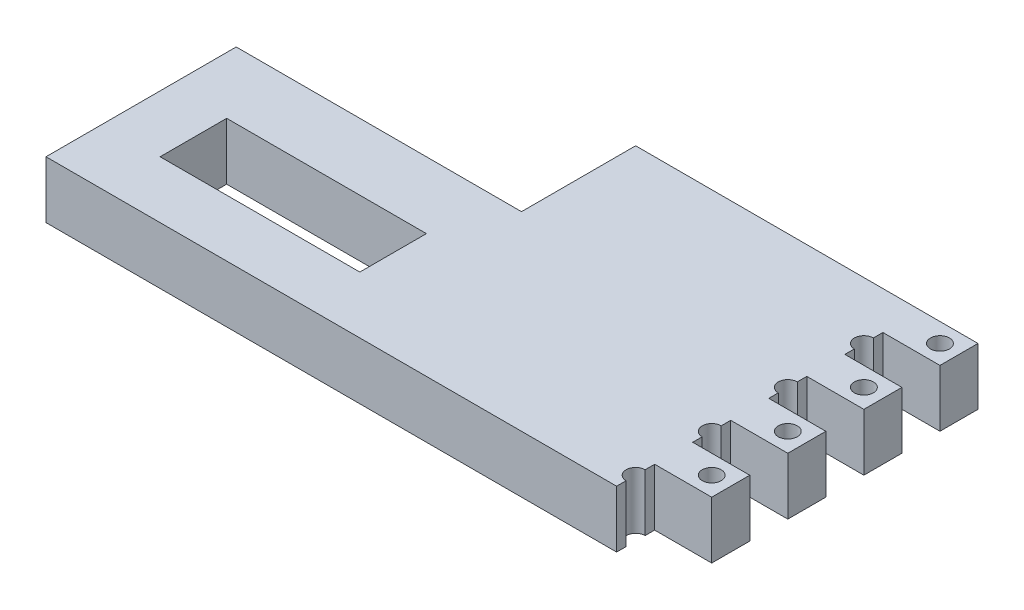
SolidWorks part; units mm, degrees
ref_plane "Front Plane" through (0, 0, 0) normal (0, 0, 1) x (1, 0, 0)
ref_plane "Top Plane" through (0, 0, 0) normal (0, 1, 0) x (1, 0, 0)
ref_plane "Right Plane" through (0, 0, 0) normal (1, 0, 0) x (0, 0, -1)
sketch "Sketch1" plane through (0, 0, 0) normal (0, 1, 0) x (1, 0, 0)
  line L0 (-30, 0) -> (0, 0)
  line L1 (0, 0) -> (0, 12)
  line L2 (0, 12) -> (36, 12)
  line L3 (36, 0) -> (36, 4)
  line L4 (36, 4) -> (30, 4)
  line L5 (30, 4) -> (30, 8)
  line L6 (30, 8) -> (36, 8)
  line L7 (36, 8) -> (36, 12)
  line L8 (30, -4) -> (36, -4)
  line L9 (36, -4) -> (36, -8)
  line L10 (36, -8) -> (30, -8)
  line L11 (30, -12) -> (30, -8)
  line L12 (36, 0) -> (30, 0)
  line L13 (30, 0) -> (30, -4)
  line L14 (30, -20) -> (-30, -20)
  line L15 (-30, -20) -> (-30, 0)
  line L16 (30, -12) -> (36, -12)
  line L17 (36, -12) -> (36, -16)
  line L18 (36, -16) -> (30, -16)
  line L19 (30, -16) -> (30, -20)
  dimension "D1" = 4
  dimension "D2" = 30
  dimension "D3" = 12
  dimension "D4" = 6
  dimension "D5" = 4
  dimension "D6" = 4
  dimension "D7" = 20
  dimension "D8" = 30
  dimension "D9" = 4
  dimension "D10" = 4
  dimension "D11" = 4
  dimension "D12" = 4
extrude "Boss-Extrude1" add sketch "Sketch1" along normal blind 6
sketch "Sketch2" plane through (0, 6, 0) normal (0, 1, 0) x (1, 0, 0)
  line L0 (0, 12) -> (0, 0) construction
  line L1 (-24, -7) -> (-3, -7)
  line L2 (-24, -7) -> (-24, -14)
  line L3 (-24, -14) -> (-3, -14)
  line L4 (-3, -7) -> (-3, -14)
  line L5 (-30, -20) -> (30, -20) construction
  dimension "D1" = 7
  dimension "D2" = 21
  dimension "D3" = 3
  dimension "D4" = 6
extrude "Cut-Extrude1" cut sketch "Sketch2" against normal through all
sketch "Sketch3" plane through (0, 6, 0) normal (0, 1, 0) x (1, 0, 0)
  line L0 (36, 8) -> (36, 12) construction
  line L1 (36, 0) -> (36, 4) construction
  line L2 (36, -8) -> (36, -4) construction
  line L3 (36, -16) -> (36, -12) construction
  line L4 (30, 4) -> (30, 8) construction
  line L5 (30, -4) -> (30, 0) construction
  line L6 (30, -12) -> (30, -8) construction
  line L7 (30, -20) -> (30, -16) construction
  circle A0 centre (34, 10) radius 1
  circle A1 centre (34, 2) radius 1
  circle A2 centre (34, -6) radius 1
  circle A3 centre (34, -14) radius 1
  circle A4 centre (30, 6) radius 1
  circle A5 centre (30, -2) radius 1
  circle A6 centre (30, -10) radius 1
  circle A7 centre (30, -18) radius 1
  point P4 (36, 10)
  point P13 (36, 2)
  point P16 (36, -6)
  point P19 (36, -14)
  dimension "D1" = 2
  dimension "D2" = 2
extrude "Cut-Extrude2" cut sketch "Sketch3" against normal through all
